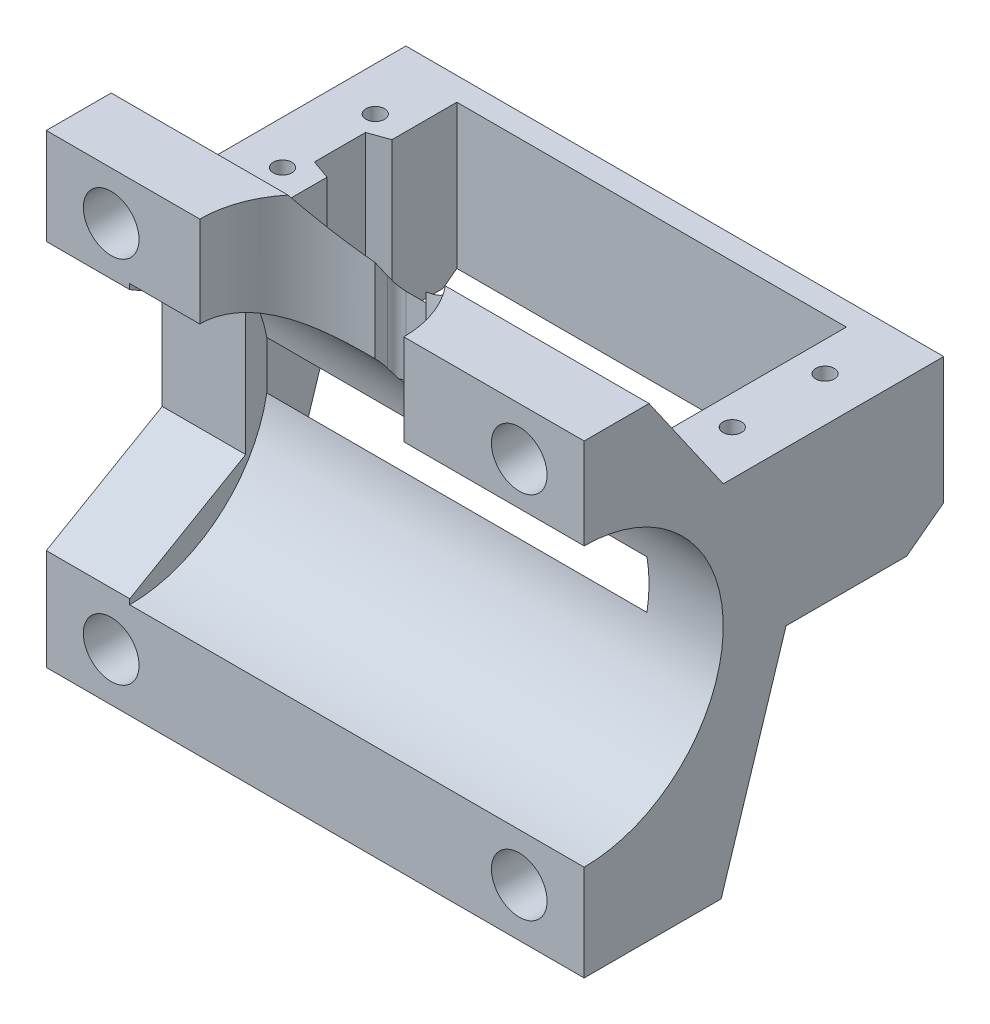
SolidWorks part; units mm, degrees
ref_plane "Front Plane" through (0, 0, 0) normal (0, 0, 1) x (1, 0, 0)
ref_plane "Top Plane" through (0, 0, 0) normal (0, 1, 0) x (1, 0, 0)
ref_plane "Right Plane" through (0, 0, 0) normal (1, 0, 0) x (0, 0, -1)
ref_plane "Plane1" through (0, -30, 0) normal (0, 1, 0) x (1, 0, 0)
sketch "Sketch1" plane through (0, -30, 0) normal (0, 1, 0) x (1, 0, 0)
  line L0 (-4.2598, -25.7738) -> (4.15, -25.7738) construction
  line L1 (29, -25.7738) -> (-29, -25.7738)
  line L2 (29, -25.7738) -> (29, 13)
  line L3 (29, 13) -> (-29, 13)
  line L4 (-29, -25.7738) -> (-29, 13)
  line L5 (29, -25.7738) -> (-29, 13) construction
  line L6 (29, 13) -> (-29, -25.7738) construction
  line L8 (27, 3.8) -> (27, -3.8) construction
  line L9 (-8.46, 10) -> (19.75, 10) construction
  line L10 (-27, -3.8) -> (-27, 3.8) construction
  line L12 (21, 10.5) -> (-21, 10.5)
  line L13 (21, 10.5) -> (21, -11)
  line L14 (21, -11) -> (-21, -11)
  line L15 (-21, 10.5) -> (-21, -11)
  point P0 (0, -6.3869)
  point P9 (-0.0549, -25.7738)
  dimension "D1" = 2
  dimension "D2" = 2.5
  dimension "D3" = 2
  dimension "D4" = 3
  dimension "D5" = 8
  dimension "D6" = 8
  dimension "D7" = 21.5
extrude "Boss-Extrude2" add sketch "Sketch1" along normal up to surface (38.65 mm away)
sketch "Sketch6" plane through (29, 0, 0) normal (1, 0, 0) x (0, 0, -1)
  line L0 (-11, -30) -> (-4, -8)
  line L1 (-25.7738, -30) -> (13, -30) construction
  line L2 (-4, -8) -> (9, -8)
  line L3 (9, -8) -> (13, -5)
  line L4 (13, 8.65) -> (13, -30) construction
  line L5 (13, -5) -> (13, -30)
  line L6 (13, -30) -> (-11, -30)
  dimension "D1" = 24
  dimension "D2" = 17
  dimension "D3" = 22
  dimension "D4" = 3
  dimension "D5" = 4
extrude "Cut-Extrude3" cut sketch "Sketch6" against normal through all
sketch "Sketch7" plane through (0, -8, 0) normal (0, -1, 0) x (1, 0, 0)
  line L0 (-21, -9) -> (-21, 4) construction
  line L1 (-21, -9) -> (-29, -9)
  line L2 (-21, -9) -> (-21, 4)
  line L3 (-21, 4) -> (-29, 4)
  line L4 (-29, -9) -> (-29, 4)
  line L5 (-29, 4) -> (-29, 11) construction
  line L6 (-29, -9) -> (-21, -9) construction
  line L7 (-29, 4) -> (-21, 4) construction
extrude "Cut-Extrude4" [suppressed] cut sketch "Sketch7" against normal blind 8
sketch "Sketch8" plane through (-29, 0, 0) normal (-1, 0, 0) x (0, 0, 1)
  line L0 (25.7738, 8.65) -> (25.7738, -30) construction
  line L1 (25.7738, 9.7838) -> (13.2738, 2.5669)
  line L2 (13.2738, 2.5669) -> (13.2738, -11.8669)
  line L3 (13.2738, -11.8669) -> (25.7738, -19.0838)
  line L4 (25.7738, -19.0838) -> (38.2738, -11.8669)
  line L5 (38.2738, -11.8669) -> (38.2738, 2.5669)
  line L6 (38.2738, 2.5669) -> (25.7738, 9.7838)
  circle A0 centre (25.7738, -4.65) radius 12.5 construction
  dimension "D1" = 12.5
sketch "Sketch9" plane through (-29, 0, 0) normal (-1, 0, 0) x (0, 0, 1)
  line L0 (10.7738, 8.65) -> (18.7738, 20.15)
  line L1 (25.7738, 8.65) -> (-13, 8.65) construction
  line L2 (18.7738, 20.15) -> (25.7738, 20.15)
  line L3 (25.7738, 20.15) -> (25.7738, 8.65)
  line L4 (10.7738, 8.65) -> (25.7738, 8.65)
  dimension "D1" = 7
  dimension "D2" = 11.5
  dimension "D3" = 15
extrude "Boss-Extrude3" add sketch "Sketch9" against normal up to surface (58 mm away) up to face at (29, -9.1, 4.5068)
extrude "Cut-Extrude5" cut sketch "Sketch8" against normal through all
sketch "Sketch10" plane through (0, 20.15, 0) normal (0, 1, 0) x (1, 0, 0)
  line L0 (29, -25.7738) -> (-29, -25.7738) construction
  line L1 (-4.2, -25.7738) -> (1.3, -25.7738)
  line L2 (-4.2, -25.7738) -> (-4.2, -12.7738)
  line L3 (-4.2, -12.7738) -> (1.3, -12.7738)
  line L4 (1.3, -25.7738) -> (1.3, -12.7738)
  circle A0 centre (-1.45, -25.7738) radius 11
  arc A1 (-7.95, -25.7738) -> (5.05, -25.7738) centre (-1.45, -25.7738) ccw construction
  point P11 (-1.45, -12.7738)
  line M7 (29, -18.7738) -> (-29, -18.7738)
  line M9 (-29, -25.7738) -> (29, -25.7738)
  dimension "D1" = 22
  dimension "D2" = 5.5
  dimension "D3" = 13
extrude "Cut-Extrude6" cut sketch "Sketch10" against normal blind 17 contours A0 L4 L3 L2 | A0 L4 M9 M7 | A0 L4 M7 | L4 A0 L2 M7 | A0 L2 M7 M9 | L4 L2 M9 M7 | L2 A0 M7 region at (-1.45, 20.15, 22.2738) region at (-7.9633, 20.15, 22.4652) region at (5.0633, 20.15, 22.4652) region at (-6.3152, 20.15, 17.4069) region at (-1.45, 20.15, 16.8303) region at (3.4152, 20.15, 17.4069) region at (-1.45, 20.15, 13.8342)
fillet "Fillet1" radius 1 2 edges at (1.3, 7.3375, 12.7738) (-4.2, 7.3375, 12.7738)
sketch "Sketch11" plane through (0, 0, 0) normal (1, 0, 0) x (0, 0, -1)
  circle A0 centre (-25.7738, -4.65) radius 15
  dimension "D1" = 30
extrude "Cut-Extrude7" cut sketch "Sketch11" against normal blind 20 and the other way through all contours A0
sketch "Sketch12" plane through (0, 0, 25.7738) normal (0, 0, 1) x (1, 0, 0)
  line L0 (-29, -4.925) -> (29, -4.925) construction
  line L1 (-29, 20.15) -> (-29, 9.7838) construction
  line L2 (29, 20.15) -> (29, 10.35) construction
  line L3 (-29, -30) -> (29, -30) construction
  line L4 (29, 20.15) -> (9.55, 20.15) construction
  circle A0 centre (-22, 14.9669) radius 3
  circle A1 centre (22, 14.9669) radius 3
  circle A2 centre (22, -24.8169) radius 3
  circle A3 centre (-22, -24.8169) radius 3
  point P14 (-29, 14.9669)
  dimension "D1" = 6
  dimension "D2" = 7
  dimension "D3" = 7
extrude "Cut-Extrude8" cut sketch "Sketch12" against normal blind 20
sketch "Sketch13" plane through (0, 0, 0) normal (0, 0, 1) x (1, 0, 0)
  line L0 (-29, -4.925) -> (29, -4.925) construction
  line L1 (29, 8.65) -> (29, -5) construction
  line L2 (-29, 8.65) -> (-29, -5) construction
  line L3 (29, 20.15) -> (7.0353, 20.15) construction
  line L4 (-21, -30) -> (21, -30) construction
  circle A0 centre (22, 14.9669) radius 4
  circle A1 centre (-22, 14.9669) radius 4
  circle A2 centre (22, -24.8169) radius 4
  circle A3 centre (-22, -24.8169) radius 4
  dimension "D1" = 8
extrude "Cut-Extrude9" cut sketch "Sketch13" along normal blind 20
sketch "Sketch15" plane through (0, 8.65, 0) normal (0, 1, 0) x (1, 0, 0)
  line L0 (29, 13) -> (29, -10.7738) construction
  line L1 (-29, 0) -> (29, 0) construction
  line L2 (-29, -10.7738) -> (-29, 13) construction
  circle A0 centre (-24.3, 5) radius 1
  circle A1 centre (-24.3, -5) radius 1
  circle A2 centre (24.2, 5) radius 1
  circle A3 centre (24.2, -5) radius 1
  dimension "D1" = 2
  dimension "D2" = 2
  dimension "D3" = 48.5
extrude "Cut-Extrude10" cut sketch "Sketch15" against normal blind 10
sketch "Sketch17" plane through (0, 8.65, 0) normal (0, 1, 0) x (1, 0, 0)
  line L5 (-21, 0) -> (-23.1, 0) construction
  line L6 (-21, -10.7738) -> (-21, 10.5) construction
  line L7 (-21, -3.5) -> (-21, 3.5)
  line L8 (-21, 3.5) -> (-23.1, 2.75)
  line L9 (-23.1, 2.75) -> (-23.1, -2.75)
  line L10 (-21, -3.5) -> (-23.1, -2.75)
  dimension "D1" = 7
  dimension "D2" = 5.5
  dimension "D3" = 2.1
extrude "Cut-Extrude11" cut sketch "Sketch17" against normal through all
